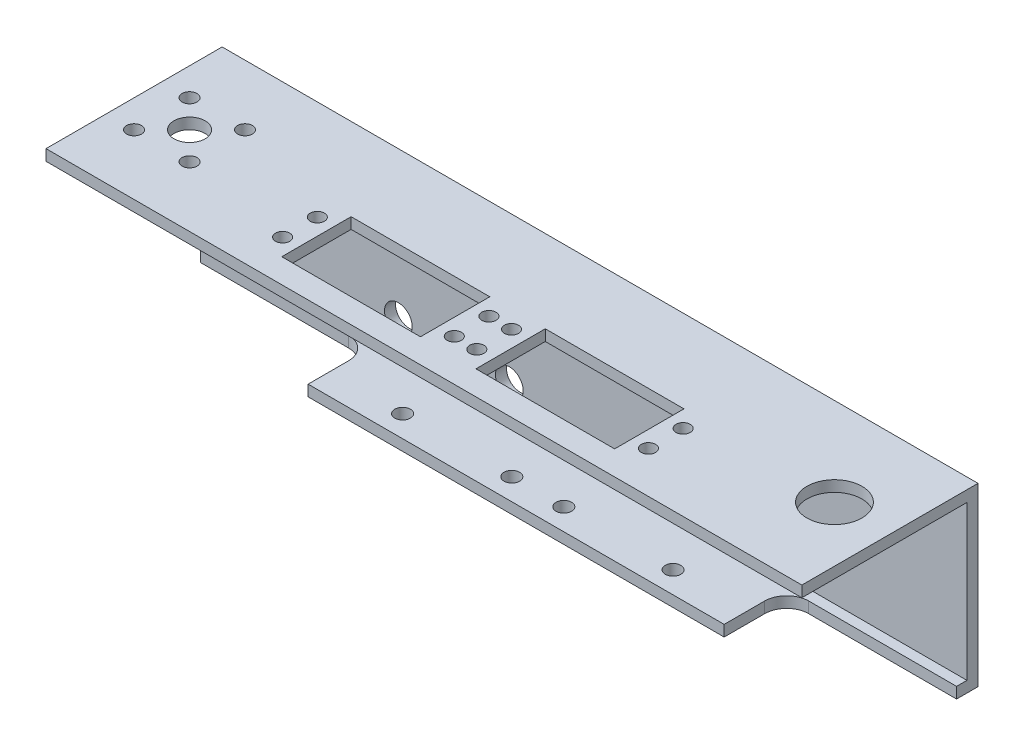
SolidWorks part; units mm, degrees
material "6061 Alloy"
ref_plane "Front Plane" through (0, 0, 0) normal (0, 0, 1) x (1, 0, 0)
ref_plane "Top Plane" through (0, 0, 0) normal (0, 1, 0) x (1, 0, 0)
ref_plane "Right Plane" through (0, 0, 0) normal (1, 0, 0) x (0, 0, -1)
sketch "Sketch1" plane through (0, 0, 0) normal (1, 0, 0) x (0, 0, -1)
  line L0 (0, 0) -> (50.8, 0)
  line L1 (50.8, 0) -> (50.8, -3.175)
  line L2 (50.8, -3.175) -> (3.175, -3.175)
  line L3 (3.175, -3.175) -> (3.175, -47.625)
  line L5 (0, -50.8) -> (0, 0)
  line L6 (0, -50.8) -> (50.8, -50.8)
  line L7 (50.8, -50.8) -> (50.8, -47.625)
  line L8 (50.8, -47.625) -> (3.175, -47.625)
  line L9 (3.175, -47.625) -> (0, -47.625) construction
  dimension "D1" = 50.8
extrude "Base Angle Profile" add sketch "Sketch1" along normal mid plane 218
sketch "Sketch2" plane through (0, 0, 0) normal (0, 1, 0) x (1, 0, 0)
  line L1 (-48, 43.8) -> (-8, 43.8)
  line L2 (-48, 43.8) -> (-48, 23.8)
  line L3 (-48, 23.8) -> (-8, 23.8)
  line L4 (-8, 43.8) -> (-8, 23.8)
  line L5 (-48, 43.8) -> (-8, 23.8) construction
  line L6 (-48, 23.8) -> (-8, 43.8) construction
  line L7 (8, 43.8) -> (48, 43.8)
  line L8 (8, 43.8) -> (8, 23.8)
  line L9 (8, 23.8) -> (48, 23.8)
  line L10 (48, 43.8) -> (48, 23.8)
  line L11 (8, 43.8) -> (48, 23.8) construction
  line L12 (8, 23.8) -> (48, 43.8) construction
  line L13 (-52.75, 38.8) -> (-52.75, 28.8) construction
  line L14 (-3.25, 28.8) -> (-3.25, 38.8) construction
  line L15 (3.25, 28.8) -> (3.25, 38.8) construction
  line L16 (52.75, 28.8) -> (52.75, 38.8) construction
  line L17 (109, 50.8) -> (-109, 50.8) construction
  line L18 (-3.25, 33.8) -> (3.25, 33.8) construction
  circle A0 centre (-52.75, 38.8) radius 2.05
  circle A1 centre (-52.75, 28.8) radius 2.05
  circle A2 centre (-3.25, 38.8) radius 2.05
  circle A3 centre (-3.25, 28.8) radius 2.05
  circle A4 centre (3.25, 28.8) radius 2.05
  circle A5 centre (3.25, 38.8) radius 2.05
  circle A6 centre (52.75, 38.8) radius 2.05
  circle A7 centre (52.75, 28.8) radius 2.05
  point P4 (-28, 33.8)
  point P9 (28, 33.8)
  point P10 (0, 33.8)
  point P28 (-52.75, 33.8)
  dimension "D5" = 4.1
  dimension "D1" = 20
  dimension "D2" = 40
  dimension "D3" = 16
  dimension "D6" = 4.75
  dimension "D7" = 10
  dimension "D8" = 4.75
  dimension "D9" = 4.75
  dimension "D10" = 4.75
  dimension "D11" = 7
extrude "Servo Mount Pattern" cut sketch "Sketch2" against normal up to surface (3.175 mm away) up to face at (0, -3.175, -26.9875)
sketch "Sketch3" plane through (0, 0, 0) normal (0, 1, 0) x (1, 0, 0)
  line L0 (93, 25.4) -> (109, 25.4) construction
  line L1 (101, 33.4) -> (85, 33.4) construction
  line L2 (101, 33.4) -> (101, 17.4) construction
  line L3 (101, 17.4) -> (85, 17.4) construction
  line L4 (85, 33.4) -> (85, 17.4) construction
  line L5 (101, 33.4) -> (85, 17.4) construction
  line L6 (101, 17.4) -> (85, 33.4) construction
  line L7 (109, 50.8) -> (109, 0) construction
  line L10 (48, 23.8) -> (48, 43.8) construction
  circle A0 centre (93, 25.4) radius 4.5
  circle A1 centre (101, 33.4) radius 2.15
  circle A2 centre (85, 33.4) radius 2.15
  circle A3 centre (85, 17.4) radius 2.15
  circle A4 centre (101, 17.4) radius 2.15
  circle A5 centre (93, 25.4) radius 16 construction
  point P7 (93, 25.4)
  dimension "D1" = 4.3
  dimension "D2" = 9
  dimension "D6" = 32
  dimension "D3" = 16
  dimension "D4" = 16
  dimension "D5" = 45
extrude "Lead Screw Nut Pattern" cut sketch "Sketch3" against normal up to surface (3.175 mm away) up to face at (52.75, -3.175, -36.75)
sketch "Sketch4" plane through (0, 0, 0) normal (0, 1, 0) x (1, 0, 0)
  line L1 (93, 25.4) -> (-93, 25.4) construction
  circle A0 centre (-93, 25.4) radius 7.9375
  circle A1 centre (-52.75, 28.8) radius 2.05 construction
  dimension "D1" = 15.875
  dimension "D2" = 40.25
extrude "Support Shaft Pass Through" cut sketch "Sketch4" against normal up to surface (3.175 mm away) up to face at (101, -3.175, -15.25)
sketch "Sketch5" plane through (0, -50.8, 0) normal (0, -1, 0) x (1, 0, 0)
  line L0 (-109, -6.175) -> (-60, -6.175)
  line L1 (-109, 0) -> (-109, -50.8) construction
  line L2 (-60, -6.175) -> (-60, -24.205)
  line L3 (-60, -24.205) -> (60, -24.205)
  line L4 (60, -24.205) -> (60, -6.175)
  line L5 (60, -6.175) -> (109, -6.175)
  line L6 (109, 0) -> (109, -50.8) construction
  line L7 (109, -6.175) -> (109, -50.8)
  line L8 (109, -50.8) -> (-109, -50.8)
  line L9 (-109, -50.8) -> (-109, -6.175)
  line L10 (109, 0) -> (-109, 0) construction
  point P16 (0, -24.205)
  dimension "D1" = 6.175
  dimension "D2" = 18.03
  dimension "D3" = 120
extrude "Channel Bottom Cut" cut sketch "Sketch5" against normal blind 10
sketch "Sketch7" plane through (0, 0, -3.175) normal (0, 0, -1) x (-1, 0, 0)
  line L0 (-109, -47.625) -> (109, -47.625) construction
  line L1 (-60, -47.625) -> (-60, -50.8) construction
  line L2 (60, -47.625) -> (60, -50.8) construction
  circle A0 centre (-55, -39.295) radius 4
  circle A1 centre (-23, -39.295) radius 4
  circle A2 centre (23, -39.295) radius 4
  circle A3 centre (55, -39.295) radius 4
  dimension "D4" = 8
  dimension "D1" = 32
  dimension "D2" = 32
  dimension "D3" = 8.33
  dimension "D5" = 5
  dimension "D6" = 5
extrude "Cut-Extrude5" cut sketch "Sketch7" against normal through all
sketch "Sketch8" plane through (0, -50.8, 0) normal (0, -1, 0) x (-1, 0, 0)
  line L0 (60, 24.205) -> (60, 6.175) construction
  line L1 (-60, 6.175) -> (-60, 24.205) construction
  line L2 (-60, 24.205) -> (60, 24.205) construction
  circle A0 centre (39, 17.955) radius 2.25
  circle A1 centre (7.5, 17.955) radius 2.25
  circle A2 centre (-7.5, 17.955) radius 2.25
  circle A3 centre (-39, 17.955) radius 2.25
  dimension "D1" = 4.5
  dimension "D2" = 21
  dimension "D3" = 15
  dimension "D4" = 7.5
  dimension "D5" = 21
  dimension "D6" = 6.25
extrude "Cut-Extrude6" cut sketch "Sketch8" against normal up to surface (3.175 mm away) up to face at (0, -47.625, -9.9325)
fillet "Fillet1" radius 6.35 2 edges at (-60, -49.2125, -6.175) (60, -49.2125, -6.175)
move or copy body "Body-Move/Copy1" bodies to move or copy 110 copy no rotation origin (0, 0, -25.4) rotation axis (0, 1, 0) rotation angle 180
equation "\"Angle-Width\"= 25.4 * 2"
equation "\"D1@Sketch1\"=\"Angle-Width\""
equation "\"Angle-Thickness\"= 25.4 / 8"
equation "\"D8@Sketch2\"=\"D6@Sketch2\""
equation "\"D9@Sketch2\"=\"D6@Sketch2\""
equation "\"D10@Sketch2\"=\"D6@Sketch2\""
equation "\"D1@Sketch5\"=\"Angle-Thickness\"+3"
equation "\"D4@Sketch8\"=\"D3@Sketch8\"/2"
equation "\"D6@Sketch8\"=12.5/2"
